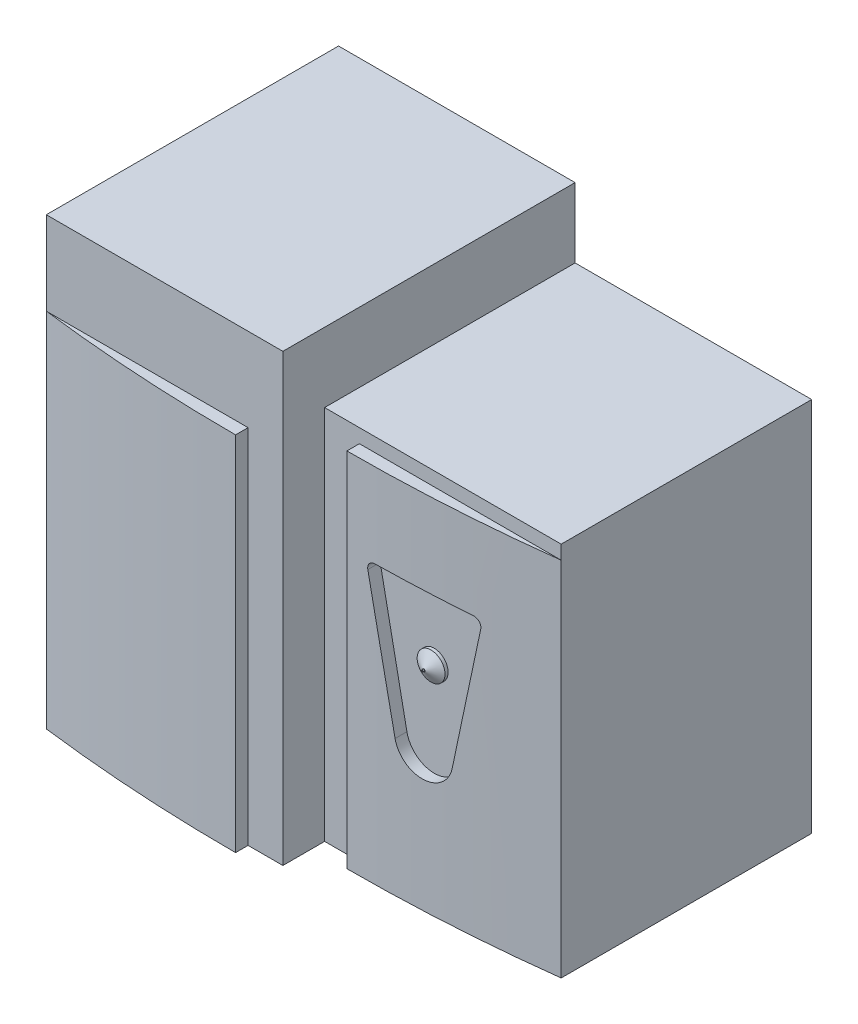
SolidWorks part; units mm, degrees
ref_plane "Front Plane" through (0, 0, 0) normal (0, 0, 1) x (1, 0, 0)
ref_plane "Top Plane" through (0, 0, 0) normal (0, 1, 0) x (1, 0, 0)
ref_plane "Right Plane" through (0, 0, 0) normal (1, 0, 0) x (0, 0, -1)
sketch "Sketch1" plane through (0, 0, 0) normal (0, 1, 0) x (1, 0, 0)
  line L1 (-215.9, 228.6) -> (215.9, 228.6)
  line L2 (-215.9, 228.6) -> (-215.9, -228.6)
  line L3 (-215.9, -228.6) -> (215.9, -228.6)
  line L4 (215.9, 228.6) -> (215.9, -228.6)
  line L5 (-215.9, 228.6) -> (215.9, -228.6) construction
  line L6 (-215.9, -228.6) -> (215.9, 228.6) construction
  point P0 (0, 0)
  dimension "D1" = 431.8
  dimension "D2" = 457.2
extrude "Boss-Extrude1" add sketch "Sketch1" along normal blind 685.8
sketch "Sketch2" plane through (0, 0, 0) normal (0, 1, 0) x (1, 0, 0)
  line L0 (-215.9, -228.6) -> (215.9, -228.6) construction
  line L1 (-215.9, 228.6) -> (-647.7, 228.6)
  line L2 (-215.9, 228.6) -> (-215.9, -304.8)
  line L3 (-215.9, -304.8) -> (-647.7, -304.8)
  line L4 (-647.7, 228.6) -> (-647.7, -304.8)
  dimension "D1" = 431.8
  dimension "D2" = 76.2
extrude "Boss-Extrude2" add sketch "Sketch2" along normal blind 812.8
sketch "Sketch4" plane through (0, 0, 0) normal (0, 1, 0) x (1, 0, 0)
  line L0 (-215.9, -251.46) -> (-152.4, -251.46) construction
  line L1 (-215.9, -304.8) -> (-215.9, 228.6) construction
  line L2 (-152.4, -251.46) -> (-152.4, -228.6)
  line L3 (-152.4, -228.6) -> (215.9, -228.6)
  line L4 (-215.9, -228.6) -> (215.9, -228.6) construction
  arc A0 (-152.4, -251.46) -> (215.9, -228.6) centre (-152.4, 2726.8311) ccw
  dimension "D1" = 22.86
  dimension "D2" = 63.5
extrude "Boss-Extrude4" add sketch "Sketch4" along normal offset from surface (660.4 mm away) 25.4 up to face at (0, 685.8, 0)
sketch "Sketch3" plane through (0, 0, 0) normal (0, 1, 0) x (1, 0, 0)
  line L0 (-279.4, -304.8) -> (-279.4, -327.66)
  line L1 (-647.7, -304.8) -> (-215.9, -304.8) construction
  line L2 (-279.4, -327.66) -> (-215.9, -327.66) construction
  line L3 (-215.9, -327.66) -> (-215.9, -304.8) construction
  line L4 (-647.7, -304.8) -> (-279.4, -304.8)
  arc A0 (-279.4, -327.66) -> (-647.7, -304.8) centre (-279.4, 2650.6311) cw
  dimension "D1" = 22.86
  dimension "D2" = 63.5
extrude "Boss-Extrude3" add sketch "Sketch3" along normal up to surface (660.4 mm away) up to face at (-29.5152, 660.4, 238.1232)
sketch "Sketch6" plane through (0, 0, 304.8) normal (0, 0, 1) x (1, 0, 0)
  line L0 (-215.9, 685.8) -> (-215.9, 0) construction
  line L1 (-152.4, 0) -> (215.9, 0) construction
  line L2 (-15.9, 507) -> (-15.9, 380) construction
  line L3 (-15.9, 380) -> (-15.9, 0) construction
  line L4 (33.9097, 248.5583) -> (82.6549, 491.8046)
  line L5 (70.2025, 507) -> (-102.0025, 507)
  line L6 (-114.4549, 491.8046) -> (-65.7097, 248.5583)
  circle A0 centre (-15.9, 380) radius 25.4 construction
  arc A1 (-65.7097, 248.5583) -> (33.9097, 248.5583) centre (-15.9, 258.5399) ccw
  arc A2 (82.6549, 491.8046) -> (70.2025, 507) centre (70.2025, 494.3) ccw
  arc A3 (-102.0025, 507) -> (-114.4549, 491.8046) centre (-102.0025, 494.3) ccw
  point P17 (85.7, 507)
  point P20 (-117.5, 507)
  dimension "D1" = 50.8
  dimension "D6" = 50.8
  dimension "D7" = 12.7
  dimension "D2" = 200
  dimension "D3" = 380
  dimension "D4" = 203.2
  dimension "D5" = 127
extrude "Cut-Extrude3" cut sketch "Sketch6" against normal up to surface (76.2 mm away) up to face at (-50.8, 448.7333, 228.6)
sketch "Sketch7" plane through (0, 0, 228.6) normal (0, 0, 1) x (1, 0, 0)
  circle A0 centre (-15.9, 380) radius 25.4
  dimension "D1" = 50.8
extrude "Boss-Extrude5" add sketch "Sketch7" along normal blind 19.05 separate body
chamfer "Chamfer1" distance 13.335 angle 60 1 edges at (9.5, 380, 247.65) first distance on face at (9.5, 380, 247.65)
ref_axis "CAPILLARY CENTERLINE" through (-15.9, 380, 411.0474) along (0, 0, -1)
sketch "Sketch8" plane through (0, 0, 247.65) normal (0, 0, 1) x (1, 0, 0)
  circle A0 centre (-15.9, 380) radius 1.5875
  circle A1 centre (-15.9, 380) radius 0.635
  dimension "D1" = 3.175
  dimension "D2" = 1.27
extrude "Boss-Extrude6" add sketch "Sketch8" along normal blind 2.54
